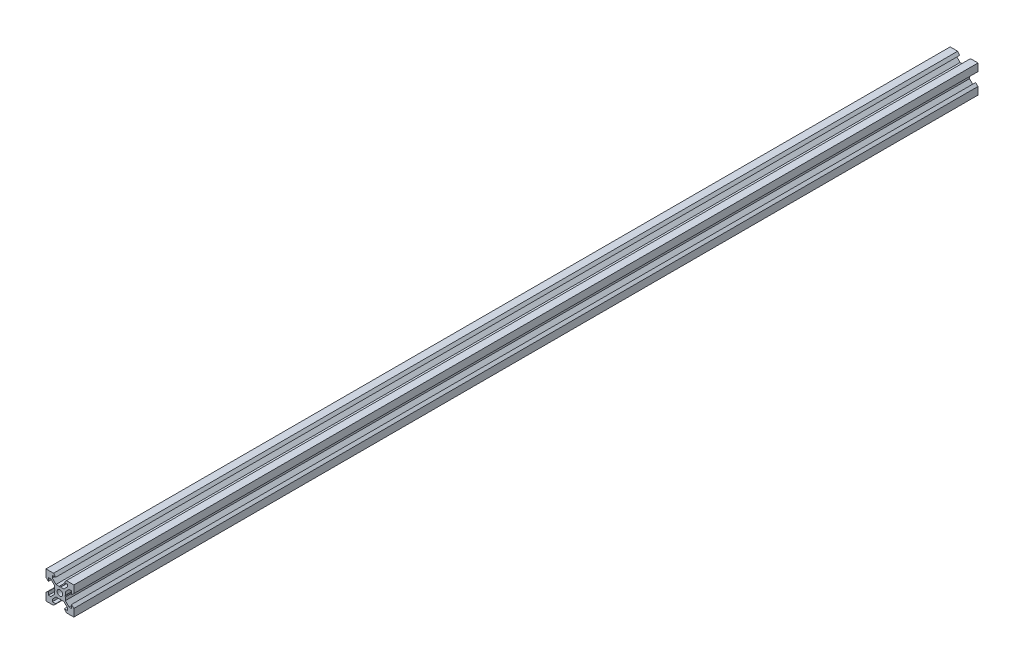
SolidWorks part; units mm, degrees
ref_plane "Front Plane" through (0, 0, 0) normal (0, 0, 1) x (1, 0, 0)
ref_plane "Top Plane" through (0, 0, 0) normal (0, 1, 0) x (1, 0, 0)
ref_plane "Right Plane" through (0, 0, 0) normal (1, 0, 0) x (0, 0, -1)
sketch "Sketch1" plane through (0, 0, 0) normal (0, 0, 1) x (1, 0, 0)
  line L0 (10, 10) -> (4.6104, 10) construction
  line L1 (10, 10) -> (10, 4.6104) construction
  line L2 (10, -10) -> (10, -4.6104) construction
  line L3 (10, -10) -> (4.6104, -10) construction
  line L4 (10, 10) -> (10, 4.6104)
  line L5 (6.5607, 5.5) -> (8.2, 5.5)
  line L6 (5.5, 8.2) -> (5.5, 6.5607)
  line L7 (10, 10) -> (4.6104, 10)
  line L8 (10, 10) -> (10, 4.6104)
  line L9 (6.5607, 5.5) -> (3.9, 2.8393)
  line L10 (5.5, 6.5607) -> (2.8393, 3.9)
  line L11 (10, 4.6104) -> (8.2, 3.1)
  line L12 (4.6104, 10) -> (3.1, 8.2)
  line L13 (8.2, 3.1) -> (8.2, 5.5)
  line L14 (3.1, 8.2) -> (5.5, 8.2)
  line L15 (-6.5607, 5.5) -> (-8.2, 5.5)
  line L16 (6.5607, -5.5) -> (8.2, -5.5)
  line L17 (3.1, -8.2) -> (5.5, -8.2)
  line L18 (8.2, -3.1) -> (8.2, -5.5)
  line L19 (4.6104, -10) -> (3.1, -8.2)
  line L20 (10, -4.6104) -> (8.2, -3.1)
  line L21 (0.5196, -3.9) -> (0, -3.6)
  line L22 (0.5196, 3.9) -> (0, 3.6)
  line L23 (3.6, 0) -> (3.9, -0.5196)
  line L24 (3.9, 0.5196) -> (3.6, 0)
  line L25 (3.9, 0.5196) -> (3.9, 2.8393)
  line L26 (2.8393, 3.9) -> (0.5196, 3.9)
  line L27 (3.9, -2.8393) -> (3.9, -0.5196)
  line L28 (2.8393, -3.9) -> (0.5196, -3.9)
  line L29 (5.5, -6.5607) -> (2.8393, -3.9)
  line L30 (6.5607, -5.5) -> (3.9, -2.8393)
  line L31 (10, -10) -> (10, -4.6104)
  line L32 (10, -10) -> (4.6104, -10)
  line L33 (5.5, -8.2) -> (5.5, -6.5607)
  line L34 (-6.5607, -5.5) -> (-8.2, -5.5)
  line L35 (10, -10) -> (10, -4.6104)
  line L36 (0, 0) -> (0, 8.2) construction
  line L37 (-10, -10) -> (-4.6104, -10) construction
  line L38 (-10, -10) -> (-10, -4.6104) construction
  line L39 (-10, 10) -> (-10, 4.6104) construction
  line L40 (-10, 10) -> (-4.6104, 10) construction
  line L41 (-10, -10) -> (-10, -4.6104)
  line L43 (-5.5, -8.2) -> (-5.5, -6.5607)
  line L44 (-10, -10) -> (-4.6104, -10)
  line L45 (-10, -10) -> (-10, -4.6104)
  line L46 (-6.5607, -5.5) -> (-3.9, -2.8393)
  line L47 (-5.5, -6.5607) -> (-2.8393, -3.9)
  line L48 (-2.8393, -3.9) -> (-0.5196, -3.9)
  line L49 (-3.9, -2.8393) -> (-3.9, -0.5196)
  line L50 (-2.8393, 3.9) -> (-0.5196, 3.9)
  line L51 (-3.9, 0.5196) -> (-3.9, 2.8393)
  line L52 (-3.9, 0.5196) -> (-3.6, 0)
  line L53 (-3.6, 0) -> (-3.9, -0.5196)
  line L54 (-0.5196, 3.9) -> (0, 3.6)
  line L55 (-0.5196, -3.9) -> (0, -3.6)
  line L56 (-10, -4.6104) -> (-8.2, -3.1)
  line L57 (-4.6104, -10) -> (-3.1, -8.2)
  line L58 (-8.2, -3.1) -> (-8.2, -5.5)
  line L59 (-3.1, -8.2) -> (-5.5, -8.2)
  line L60 (-10, -10) -> (10, -10) construction
  line L61 (-10, -10) -> (-10, 10) construction
  line L62 (-3.1, 8.2) -> (-5.5, 8.2)
  line L63 (-8.2, 3.1) -> (-8.2, 5.5)
  line L64 (-4.6104, 10) -> (-3.1, 8.2)
  line L65 (-10, 4.6104) -> (-8.2, 3.1)
  line L66 (-5.5, 6.5607) -> (-2.8393, 3.9)
  line L67 (-6.5607, 5.5) -> (-3.9, 2.8393)
  line L68 (-10, 10) -> (-10, 4.6104)
  line L69 (-10, 10) -> (-4.6104, 10)
  line L70 (-5.5, 8.2) -> (-5.5, 6.5607)
  line L71 (-10, 10) -> (10, 10) construction
  line L72 (-10, 10) -> (-10, 4.6104)
  line L73 (10, -10) -> (10, 10) construction
  line L74 (-10, -10) -> (10, 10) construction
  line L75 (-10, 10) -> (10, -10) construction
  circle A0 centre (0, 0) radius 2
  dimension "D7" = 4
  dimension "D1" = 20
  dimension "D2" = 5.3896
  dimension "D3" = 4.5
  dimension "D4" = 50
  dimension "D5" = 1.8
  dimension "D6" = 1.5104
  dimension "D8" = 5.5
  dimension "D9" = 120
  dimension "D10" = 0.3
  dimension "D11" = 2.3197
  dimension "D12" = 7.8
  dimension "D13" = 7.8
  dimension "D14" = 1.5
  dimension "D15" = 2.6607
extrude "Boss-Extrude1" add sketch "Sketch1" along normal mid plane 649.15 contours L70 L62 L64 L69 L68 L65 L63 L15 L67 L51 L52 L53 L49 L46 L34 L58 L56 L41 L44 L57 L59 L43 L47 L48 L55 L21 L28 L29 L33 L17 L19 L32 L31 L20 L18 L16 L30 L27 L23 L24 L25 L9 L5 L13 L11 L4 L7 L12 L14 L6 L10 region at (9.7172, 7.3052, 0)
